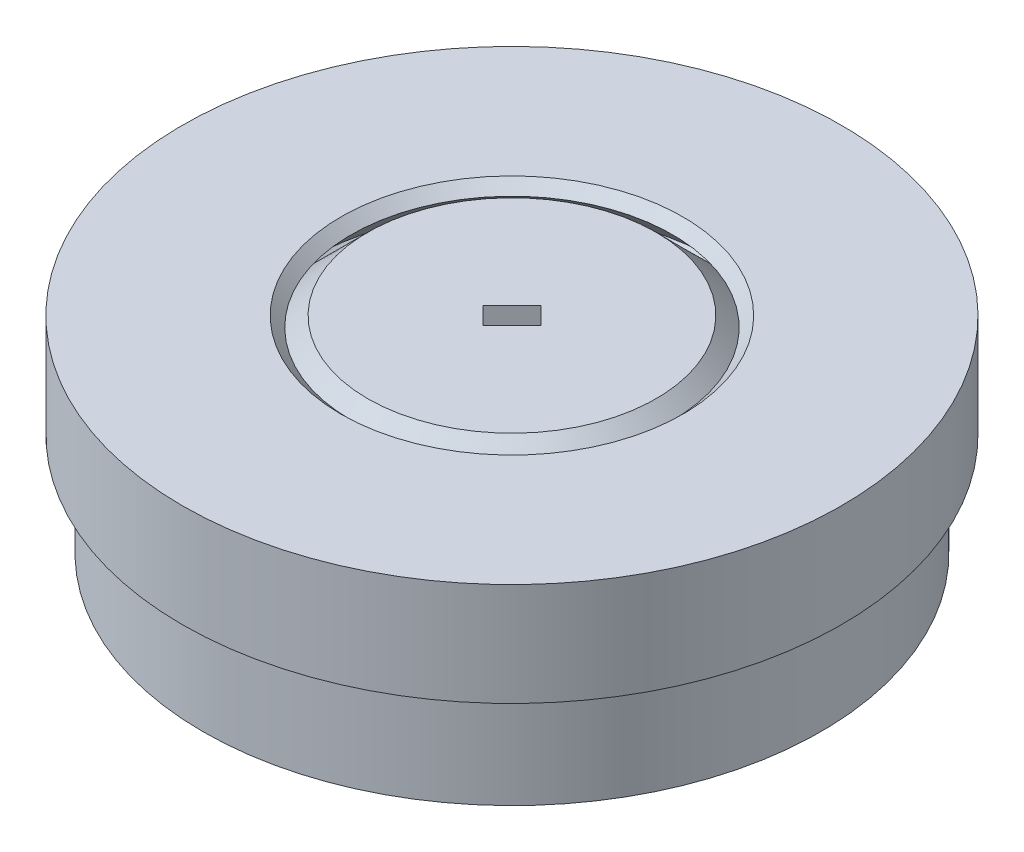
SolidWorks part; units mm, degrees
ref_plane "Front Plane" through (0, 0, 0) normal (0, 0, 1) x (1, 0, 0)
ref_plane "Top Plane" through (0, 0, 0) normal (0, 1, 0) x (1, 0, 0)
ref_plane "Right Plane" through (0, 0, 0) normal (1, 0, 0) x (0, 0, -1)
sketch "Sketch3" plane through (0, 0, 0) normal (0, 1, 0) x (1, 0, 0)
  line L0 (0, 0) -> (0, 14) construction
  line L1 (0, 11) -> (0, 14)
  line L2 (6.4656, 8.8992) -> (8.229, 11.3262)
  line L3 (10.4616, 3.3992) -> (13.3148, 4.3262)
  line L4 (10.4616, -3.3992) -> (13.3148, -4.3262)
  line L5 (6.4656, -8.8992) -> (8.229, -11.3262)
  line L6 (0, -11) -> (0, -14)
  line L7 (-6.4656, -8.8992) -> (-8.229, -11.3262)
  line L8 (-10.4616, -3.3992) -> (-13.3148, -4.3262)
  line L9 (-10.4616, 3.3992) -> (-13.3148, 4.3262)
  line L10 (-6.4656, 8.8992) -> (-8.229, 11.3262)
  line L12 (2, 2) -> (-2, 2)
  line L13 (2, 2) -> (2, -2)
  line L14 (2, -2) -> (-2, -2)
  line L15 (-2, 2) -> (-2, -2)
  line L16 (0, -2) -> (0, 2) construction
  line L17 (2, 0) -> (-2, 0) construction
  circle A0 centre (0, 0) radius 15
  circle A1 centre (0, 0) radius 14 construction
  spline S0 degree 4 poles (-0.6778, 10.6763) (-0.6286, 10.7014) (-0.5336, 10.7495) (-0.4182, 10.8106) (-0.084, 10.9641) (0.0577, 11.0264) (0.4379, 11.1818) (0.6637, 11.2619) (0.971, 11.3685) (1.234, 11.4472) (1.5272, 11.5305) (1.8056, 11.5989) (2.0959, 11.6642) (2.3817, 11.7192) (2.6725, 11.7684) (2.9623, 11.8092) (3.2542, 11.8431) (3.5945, 11.8737) (4.009, 11.8986) (4.4979, 11.9088) (4.9859, 11.897) (5.4262, 11.8684) (5.7898, 11.8338) (6.0839, 11.7981) (6.4416, 11.7478) (6.8131, 11.6815) (7.1561, 11.6125) (7.5364, 11.5205) (7.7792, 11.459) (8.1801, 11.3427) (8.3369, 11.2932) (8.7269, 11.165) (8.8594, 11.1137) (8.9726, 11.0725) (9.0307, 11.0511) knots 0 0 0 0 0 0.018755 0.037509 0.074516 0.103872 0.133229 0.162585 0.191942 0.221299 0.250655 0.280012 0.309368 0.338725 0.368082 0.397438 0.426795 0.456151 0.504872 0.563586 0.622299 0.651656 0.681012 0.710369 0.739725 0.798439 0.827795 0.857152 0.886508 0.915865 0.957933 0.978966 1 1 1 1 1 construction
  spline S1 degree 4 poles (0, 11) (0.0566, 11.0246) (0.1702, 11.0724) (0.4379, 11.1818) (0.6637, 11.2619) (0.971, 11.3685) (1.234, 11.4472) (1.5272, 11.5305) (1.8056, 11.5989) (2.0959, 11.6642) (2.3817, 11.7192) (2.6725, 11.7684) (2.9623, 11.8092) (3.2542, 11.8431) (3.5945, 11.8737) (4.009, 11.8986) (4.4979, 11.9088) (4.9859, 11.897) (5.4262, 11.8684) (5.7898, 11.8338) (6.0839, 11.7981) (6.4416, 11.7478) (6.8131, 11.6815) (7.1561, 11.6125) (7.5364, 11.5205) (7.7792, 11.459) (8.0505, 11.3803) (8.17, 11.3445) (8.229, 11.3262) knots 0.074516 0.074516 0.074516 0.074516 0.074516 0.103872 0.133229 0.162585 0.191942 0.221299 0.250655 0.280012 0.309368 0.338725 0.368082 0.397438 0.426795 0.456151 0.504872 0.563586 0.622299 0.651656 0.681012 0.710369 0.739725 0.798439 0.827795 0.857152 0.886508 0.915865 0.915865 0.915865 0.915865 0.915865
  spline S2 degree 4 poles (5.727, 9.0357) (5.7816, 9.0271) (5.8867, 9.0101) (6.016, 8.9918) (6.3766, 8.9195) (6.5279, 8.8866) (6.9268, 8.7889) (7.1565, 8.7209) (7.4678, 8.6266) (7.7268, 8.5357) (8.013, 8.4307) (8.2785, 8.3224) (8.5517, 8.2045) (8.8152, 8.0811) (9.0794, 7.95) (9.3378, 7.8126) (9.5939, 7.6685) (9.8872, 7.4932) (10.2371, 7.2697) (10.6387, 6.9906) (11.0265, 6.6943) (11.3659, 6.4123) (11.6398, 6.1706) (11.8567, 5.9689) (12.1165, 5.7179) (12.3781, 5.4459) (12.6151, 5.1885) (12.8687, 4.8905) (13.029, 4.698) (13.2848, 4.3683) (13.3827, 4.236) (13.6228, 3.9031) (13.6999, 3.7838) (13.7672, 3.6839) (13.8017, 3.6324) knots 0 0 0 0 0 0.018755 0.037509 0.074516 0.103872 0.133229 0.162585 0.191942 0.221299 0.250655 0.280012 0.309368 0.338725 0.368082 0.397438 0.426795 0.456151 0.504872 0.563586 0.622299 0.651656 0.681012 0.710369 0.739725 0.798439 0.827795 0.857152 0.886508 0.915865 0.957933 0.978966 1 1 1 1 1 construction
  spline S3 degree 4 poles (6.4656, 8.8992) (6.5259, 8.8858) (6.6459, 8.8577) (6.9268, 8.7889) (7.1565, 8.7209) (7.4678, 8.6266) (7.7268, 8.5357) (8.013, 8.4307) (8.2785, 8.3224) (8.5517, 8.2045) (8.8152, 8.0811) (9.0794, 7.95) (9.3378, 7.8126) (9.5939, 7.6685) (9.8872, 7.4932) (10.2371, 7.2697) (10.6387, 6.9906) (11.0265, 6.6943) (11.3659, 6.4123) (11.6398, 6.1706) (11.8567, 5.9689) (12.1165, 5.7179) (12.3781, 5.4459) (12.6151, 5.1885) (12.8687, 4.8905) (13.029, 4.698) (13.2021, 4.4749) (13.2778, 4.3756) (13.3148, 4.3262) knots 0.074516 0.074516 0.074516 0.074516 0.074516 0.103872 0.133229 0.162585 0.191942 0.221299 0.250655 0.280012 0.309368 0.338725 0.368082 0.397438 0.426795 0.456151 0.504872 0.563586 0.622299 0.651656 0.681012 0.710369 0.739725 0.798439 0.827795 0.857152 0.886508 0.915865 0.915865 0.915865 0.915865 0.915865
  spline S4 degree 4 poles (9.9443, 3.9438) (9.9834, 3.9047) (10.0585, 3.8292) (10.1522, 3.7384) (10.4015, 3.468) (10.5046, 3.3524) (10.7698, 3.0389) (10.9158, 2.8489) (11.1122, 2.5895) (11.2683, 2.3638) (11.4381, 2.1106) (11.5892, 1.867) (11.7409, 1.6111) (11.8816, 1.3563) (12.0183, 1.095) (12.1466, 0.8319) (12.2691, 0.5648) (12.4033, 0.2506) (12.5551, -0.1359) (12.7158, -0.5977) (12.8555, -1.0654) (12.9643, -1.493) (13.0438, -1.8496) (13.1007, -2.1403) (13.1634, -2.496) (13.2151, -2.8698) (13.2555, -3.2174) (13.2855, -3.6076) (13.3021, -3.8575) (13.3153, -4.2746) (13.3167, -4.4391) (13.3153, -4.8496) (13.3075, -4.9915) (13.3032, -5.1118) (13.3009, -5.1737) knots 0 0 0 0 0 0.018755 0.037509 0.074516 0.103872 0.133229 0.162585 0.191942 0.221299 0.250655 0.280012 0.309368 0.338725 0.368082 0.397438 0.426795 0.456151 0.504872 0.563586 0.622299 0.651656 0.681012 0.710369 0.739725 0.798439 0.827795 0.857152 0.886508 0.915865 0.957933 0.978966 1 1 1 1 1 construction
  spline S5 degree 4 poles (10.4616, 3.3992) (10.5025, 3.3529) (10.583, 3.2597) (10.7698, 3.0389) (10.9158, 2.8489) (11.1122, 2.5895) (11.2683, 2.3638) (11.4381, 2.1106) (11.5892, 1.867) (11.7409, 1.6111) (11.8816, 1.3563) (12.0183, 1.095) (12.1466, 0.8319) (12.2691, 0.5648) (12.4033, 0.2506) (12.5551, -0.1359) (12.7158, -0.5977) (12.8555, -1.0654) (12.9643, -1.493) (13.0438, -1.8496) (13.1007, -2.1403) (13.1634, -2.496) (13.2151, -2.8698) (13.2555, -3.2174) (13.2855, -3.6076) (13.3021, -3.8575) (13.311, -4.1398) (13.3139, -4.2645) (13.3148, -4.3262) knots 0.074516 0.074516 0.074516 0.074516 0.074516 0.103872 0.133229 0.162585 0.191942 0.221299 0.250655 0.280012 0.309368 0.338725 0.368082 0.397438 0.426795 0.456151 0.504872 0.563586 0.622299 0.651656 0.681012 0.710369 0.739725 0.798439 0.827795 0.857152 0.886508 0.915865 0.915865 0.915865 0.915865 0.915865
  spline S6 degree 4 poles (10.3632, -2.6545) (10.3719, -2.7091) (10.3882, -2.8143) (10.4107, -2.9429) (10.4535, -3.3082) (10.4689, -3.4622) (10.4992, -3.8718) (10.5056, -4.1113) (10.512, -4.4366) (10.5056, -4.711) (10.4942, -5.0156) (10.4732, -5.3015) (10.4456, -5.5978) (10.4097, -5.8866) (10.3666, -6.1783) (10.3158, -6.4665) (10.2579, -6.7546) (10.1818, -7.0878) (10.0774, -7.4896) (9.936, -7.9578) (9.774, -8.4182) (9.6108, -8.8281) (9.4655, -9.1633) (9.3407, -9.4319) (9.1823, -9.7566) (9.0044, -10.0894) (8.8328, -10.3943) (8.6277, -10.7276) (8.4943, -10.9395) (8.2597, -11.2848) (8.1642, -11.4187) (7.9218, -11.7499) (7.8321, -11.8601) (7.7579, -11.955) (7.7196, -12.0037) knots 0 0 0 0 0 0.018755 0.037509 0.074516 0.103872 0.133229 0.162585 0.191942 0.221299 0.250655 0.280012 0.309368 0.338725 0.368082 0.397438 0.426795 0.456151 0.504872 0.563586 0.622299 0.651656 0.681012 0.710369 0.739725 0.798439 0.827795 0.857152 0.886508 0.915865 0.957933 0.978966 1 1 1 1 1 construction
  spline S7 degree 4 poles (10.4616, -3.3992) (10.4675, -3.4606) (10.4779, -3.5834) (10.4992, -3.8718) (10.5056, -4.1113) (10.512, -4.4366) (10.5056, -4.711) (10.4942, -5.0156) (10.4732, -5.3015) (10.4456, -5.5978) (10.4097, -5.8866) (10.3666, -6.1783) (10.3158, -6.4665) (10.2579, -6.7546) (10.1818, -7.0878) (10.0774, -7.4896) (9.936, -7.9578) (9.774, -8.4182) (9.6108, -8.8281) (9.4655, -9.1633) (9.3407, -9.4319) (9.1823, -9.7566) (9.0044, -10.0894) (8.8328, -10.3943) (8.6277, -10.7276) (8.4943, -10.9395) (8.3355, -11.1732) (8.2645, -11.2758) (8.229, -11.3262) knots 0.074516 0.074516 0.074516 0.074516 0.074516 0.103872 0.133229 0.162585 0.191942 0.221299 0.250655 0.280012 0.309368 0.338725 0.368082 0.397438 0.426795 0.456151 0.504872 0.563586 0.622299 0.651656 0.681012 0.710369 0.739725 0.798439 0.827795 0.857152 0.886508 0.915865 0.915865 0.915865 0.915865 0.915865
  spline S8 degree 4 poles (6.8238, -8.2389) (6.7987, -8.2881) (6.75, -8.3829) (6.6926, -8.5001) (6.5125, -8.8208) (6.4344, -8.9545) (6.2182, -9.3037) (6.0826, -9.5012) (5.8967, -9.7681) (5.7302, -9.9863) (5.5419, -10.2261) (5.3569, -10.445) (5.1604, -10.6685) (4.9615, -10.881) (4.7552, -11.0917) (4.5447, -11.295) (4.3285, -11.4941) (4.0712, -11.7188) (3.7505, -11.9826) (3.3609, -12.2782) (2.9593, -12.5555) (2.5862, -12.7912) (2.2717, -12.9769) (2.0128, -13.1209) (1.6938, -13.2904) (1.3544, -13.4552) (1.0362, -13.601) (0.6745, -13.7501) (0.4419, -13.8431) (0.0492, -13.9845) (-0.1068, -14.0367) (-0.4976, -14.1622) (-0.6349, -14.1986) (-0.7507, -14.2318) (-0.8103, -14.2487) knots 0 0 0 0 0 0.018755 0.037509 0.074516 0.103872 0.133229 0.162585 0.191942 0.221299 0.250655 0.280012 0.309368 0.338725 0.368082 0.397438 0.426795 0.456151 0.504872 0.563586 0.622299 0.651656 0.681012 0.710369 0.739725 0.798439 0.827795 0.857152 0.886508 0.915865 0.957933 0.978966 1 1 1 1 1 construction
  spline S9 degree 4 poles (6.4656, -8.8992) (6.4343, -8.9523) (6.3705, -9.0578) (6.2182, -9.3037) (6.0826, -9.5012) (5.8967, -9.7681) (5.7302, -9.9863) (5.5419, -10.2261) (5.3569, -10.445) (5.1604, -10.6685) (4.9615, -10.881) (4.7552, -11.0917) (4.5447, -11.295) (4.3285, -11.4941) (4.0712, -11.7188) (3.7505, -11.9826) (3.3609, -12.2782) (2.9593, -12.5555) (2.5862, -12.7912) (2.2717, -12.9769) (2.0128, -13.1209) (1.6938, -13.2904) (1.3544, -13.4552) (1.0362, -13.601) (0.6745, -13.7501) (0.4419, -13.8431) (0.1762, -13.9388) (0.0584, -13.9801) (0, -14) knots 0.074516 0.074516 0.074516 0.074516 0.074516 0.103872 0.133229 0.162585 0.191942 0.221299 0.250655 0.280012 0.309368 0.338725 0.368082 0.397438 0.426795 0.456151 0.504872 0.563586 0.622299 0.651656 0.681012 0.710369 0.739725 0.798439 0.827795 0.857152 0.886508 0.915865 0.915865 0.915865 0.915865 0.915865
  spline S10 degree 4 poles (0.6778, -10.6763) (0.6286, -10.7014) (0.5336, -10.7495) (0.4182, -10.8106) (0.084, -10.9641) (-0.0577, -11.0264) (-0.4379, -11.1818) (-0.6637, -11.2619) (-0.971, -11.3685) (-1.234, -11.4472) (-1.5272, -11.5305) (-1.8056, -11.5989) (-2.0959, -11.6642) (-2.3817, -11.7192) (-2.6725, -11.7684) (-2.9623, -11.8092) (-3.2542, -11.8431) (-3.5945, -11.8737) (-4.009, -11.8986) (-4.4979, -11.9088) (-4.9859, -11.897) (-5.4262, -11.8684) (-5.7898, -11.8338) (-6.0839, -11.7981) (-6.4416, -11.7478) (-6.8131, -11.6815) (-7.1561, -11.6125) (-7.5364, -11.5205) (-7.7792, -11.459) (-8.1801, -11.3427) (-8.3369, -11.2932) (-8.7269, -11.165) (-8.8594, -11.1137) (-8.9726, -11.0725) (-9.0307, -11.0511) knots 0 0 0 0 0 0.018755 0.037509 0.074516 0.103872 0.133229 0.162585 0.191942 0.221299 0.250655 0.280012 0.309368 0.338725 0.368082 0.397438 0.426795 0.456151 0.504872 0.563586 0.622299 0.651656 0.681012 0.710369 0.739725 0.798439 0.827795 0.857152 0.886508 0.915865 0.957933 0.978966 1 1 1 1 1 construction
  spline S11 degree 4 poles (0, -11) (-0.0566, -11.0246) (-0.1702, -11.0724) (-0.4379, -11.1818) (-0.6637, -11.2619) (-0.971, -11.3685) (-1.234, -11.4472) (-1.5272, -11.5305) (-1.8056, -11.5989) (-2.0959, -11.6642) (-2.3817, -11.7192) (-2.6725, -11.7684) (-2.9623, -11.8092) (-3.2542, -11.8431) (-3.5945, -11.8737) (-4.009, -11.8986) (-4.4979, -11.9088) (-4.9859, -11.897) (-5.4262, -11.8684) (-5.7898, -11.8338) (-6.0839, -11.7981) (-6.4416, -11.7478) (-6.8131, -11.6815) (-7.1561, -11.6125) (-7.5364, -11.5205) (-7.7792, -11.459) (-8.0505, -11.3803) (-8.17, -11.3445) (-8.229, -11.3262) knots 0.074516 0.074516 0.074516 0.074516 0.074516 0.103872 0.133229 0.162585 0.191942 0.221299 0.250655 0.280012 0.309368 0.338725 0.368082 0.397438 0.426795 0.456151 0.504872 0.563586 0.622299 0.651656 0.681012 0.710369 0.739725 0.798439 0.827795 0.857152 0.886508 0.915865 0.915865 0.915865 0.915865 0.915865
  spline S12 degree 4 poles (-5.727, -9.0357) (-5.7816, -9.0271) (-5.8867, -9.0101) (-6.016, -8.9918) (-6.3766, -8.9195) (-6.5279, -8.8866) (-6.9268, -8.7889) (-7.1565, -8.7209) (-7.4678, -8.6266) (-7.7268, -8.5357) (-8.013, -8.4307) (-8.2785, -8.3224) (-8.5517, -8.2045) (-8.8152, -8.0811) (-9.0794, -7.95) (-9.3378, -7.8126) (-9.5939, -7.6685) (-9.8872, -7.4932) (-10.2371, -7.2697) (-10.6387, -6.9906) (-11.0265, -6.6943) (-11.3659, -6.4123) (-11.6398, -6.1706) (-11.8567, -5.9689) (-12.1165, -5.7179) (-12.3781, -5.4459) (-12.6151, -5.1885) (-12.8687, -4.8905) (-13.029, -4.698) (-13.2848, -4.3683) (-13.3827, -4.236) (-13.6228, -3.9031) (-13.6999, -3.7838) (-13.7672, -3.6839) (-13.8017, -3.6324) knots 0 0 0 0 0 0.018755 0.037509 0.074516 0.103872 0.133229 0.162585 0.191942 0.221299 0.250655 0.280012 0.309368 0.338725 0.368082 0.397438 0.426795 0.456151 0.504872 0.563586 0.622299 0.651656 0.681012 0.710369 0.739725 0.798439 0.827795 0.857152 0.886508 0.915865 0.957933 0.978966 1 1 1 1 1 construction
  spline S13 degree 4 poles (-6.4656, -8.8992) (-6.5259, -8.8858) (-6.6459, -8.8577) (-6.9268, -8.7889) (-7.1565, -8.7209) (-7.4678, -8.6266) (-7.7268, -8.5357) (-8.013, -8.4307) (-8.2785, -8.3224) (-8.5517, -8.2045) (-8.8152, -8.0811) (-9.0794, -7.95) (-9.3378, -7.8126) (-9.5939, -7.6685) (-9.8872, -7.4932) (-10.2371, -7.2697) (-10.6387, -6.9906) (-11.0265, -6.6943) (-11.3659, -6.4123) (-11.6398, -6.1706) (-11.8567, -5.9689) (-12.1165, -5.7179) (-12.3781, -5.4459) (-12.6151, -5.1885) (-12.8687, -4.8905) (-13.029, -4.698) (-13.2021, -4.4749) (-13.2778, -4.3756) (-13.3148, -4.3262) knots 0.074516 0.074516 0.074516 0.074516 0.074516 0.103872 0.133229 0.162585 0.191942 0.221299 0.250655 0.280012 0.309368 0.338725 0.368082 0.397438 0.426795 0.456151 0.504872 0.563586 0.622299 0.651656 0.681012 0.710369 0.739725 0.798439 0.827795 0.857152 0.886508 0.915865 0.915865 0.915865 0.915865 0.915865
  spline S14 degree 4 poles (-9.9443, -3.9438) (-9.9834, -3.9047) (-10.0585, -3.8292) (-10.1522, -3.7384) (-10.4015, -3.468) (-10.5046, -3.3524) (-10.7698, -3.0389) (-10.9158, -2.8489) (-11.1122, -2.5895) (-11.2683, -2.3638) (-11.4381, -2.1106) (-11.5892, -1.867) (-11.7409, -1.6111) (-11.8816, -1.3563) (-12.0183, -1.095) (-12.1466, -0.8319) (-12.2691, -0.5648) (-12.4033, -0.2506) (-12.5551, 0.1359) (-12.7158, 0.5977) (-12.8555, 1.0654) (-12.9643, 1.493) (-13.0438, 1.8496) (-13.1007, 2.1403) (-13.1634, 2.496) (-13.2151, 2.8698) (-13.2555, 3.2174) (-13.2855, 3.6076) (-13.3021, 3.8575) (-13.3153, 4.2746) (-13.3167, 4.4391) (-13.3153, 4.8496) (-13.3075, 4.9915) (-13.3032, 5.1118) (-13.3009, 5.1737) knots 0 0 0 0 0 0.018755 0.037509 0.074516 0.103872 0.133229 0.162585 0.191942 0.221299 0.250655 0.280012 0.309368 0.338725 0.368082 0.397438 0.426795 0.456151 0.504872 0.563586 0.622299 0.651656 0.681012 0.710369 0.739725 0.798439 0.827795 0.857152 0.886508 0.915865 0.957933 0.978966 1 1 1 1 1 construction
  spline S15 degree 4 poles (-10.4616, -3.3992) (-10.5025, -3.3529) (-10.583, -3.2597) (-10.7698, -3.0389) (-10.9158, -2.8489) (-11.1122, -2.5895) (-11.2683, -2.3638) (-11.4381, -2.1106) (-11.5892, -1.867) (-11.7409, -1.6111) (-11.8816, -1.3563) (-12.0183, -1.095) (-12.1466, -0.8319) (-12.2691, -0.5648) (-12.4033, -0.2506) (-12.5551, 0.1359) (-12.7158, 0.5977) (-12.8555, 1.0654) (-12.9643, 1.493) (-13.0438, 1.8496) (-13.1007, 2.1403) (-13.1634, 2.496) (-13.2151, 2.8698) (-13.2555, 3.2174) (-13.2855, 3.6076) (-13.3021, 3.8575) (-13.311, 4.1398) (-13.3139, 4.2645) (-13.3148, 4.3262) knots 0.074516 0.074516 0.074516 0.074516 0.074516 0.103872 0.133229 0.162585 0.191942 0.221299 0.250655 0.280012 0.309368 0.338725 0.368082 0.397438 0.426795 0.456151 0.504872 0.563586 0.622299 0.651656 0.681012 0.710369 0.739725 0.798439 0.827795 0.857152 0.886508 0.915865 0.915865 0.915865 0.915865 0.915865
  spline S16 degree 4 poles (-10.3632, 2.6545) (-10.3719, 2.7091) (-10.3882, 2.8143) (-10.4107, 2.9429) (-10.4535, 3.3082) (-10.4689, 3.4622) (-10.4992, 3.8718) (-10.5056, 4.1113) (-10.512, 4.4366) (-10.5056, 4.711) (-10.4942, 5.0156) (-10.4732, 5.3015) (-10.4456, 5.5978) (-10.4097, 5.8866) (-10.3666, 6.1783) (-10.3158, 6.4665) (-10.2579, 6.7546) (-10.1818, 7.0878) (-10.0774, 7.4896) (-9.936, 7.9578) (-9.774, 8.4182) (-9.6108, 8.8281) (-9.4655, 9.1633) (-9.3407, 9.4319) (-9.1823, 9.7566) (-9.0044, 10.0894) (-8.8328, 10.3943) (-8.6277, 10.7276) (-8.4943, 10.9395) (-8.2597, 11.2848) (-8.1642, 11.4187) (-7.9218, 11.7499) (-7.8321, 11.8601) (-7.7579, 11.955) (-7.7196, 12.0037) knots 0 0 0 0 0 0.018755 0.037509 0.074516 0.103872 0.133229 0.162585 0.191942 0.221299 0.250655 0.280012 0.309368 0.338725 0.368082 0.397438 0.426795 0.456151 0.504872 0.563586 0.622299 0.651656 0.681012 0.710369 0.739725 0.798439 0.827795 0.857152 0.886508 0.915865 0.957933 0.978966 1 1 1 1 1 construction
  spline S17 degree 4 poles (-10.4616, 3.3992) (-10.4675, 3.4606) (-10.4779, 3.5834) (-10.4992, 3.8718) (-10.5056, 4.1113) (-10.512, 4.4366) (-10.5056, 4.711) (-10.4942, 5.0156) (-10.4732, 5.3015) (-10.4456, 5.5978) (-10.4097, 5.8866) (-10.3666, 6.1783) (-10.3158, 6.4665) (-10.2579, 6.7546) (-10.1818, 7.0878) (-10.0774, 7.4896) (-9.936, 7.9578) (-9.774, 8.4182) (-9.6108, 8.8281) (-9.4655, 9.1633) (-9.3407, 9.4319) (-9.1823, 9.7566) (-9.0044, 10.0894) (-8.8328, 10.3943) (-8.6277, 10.7276) (-8.4943, 10.9395) (-8.3355, 11.1732) (-8.2645, 11.2758) (-8.229, 11.3262) knots 0.074516 0.074516 0.074516 0.074516 0.074516 0.103872 0.133229 0.162585 0.191942 0.221299 0.250655 0.280012 0.309368 0.338725 0.368082 0.397438 0.426795 0.456151 0.504872 0.563586 0.622299 0.651656 0.681012 0.710369 0.739725 0.798439 0.827795 0.857152 0.886508 0.915865 0.915865 0.915865 0.915865 0.915865
  spline S18 degree 4 poles (-6.8238, 8.2389) (-6.7987, 8.2881) (-6.75, 8.3829) (-6.6926, 8.5001) (-6.5125, 8.8208) (-6.4344, 8.9545) (-6.2182, 9.3037) (-6.0826, 9.5012) (-5.8967, 9.7681) (-5.7302, 9.9863) (-5.5419, 10.2261) (-5.3569, 10.445) (-5.1604, 10.6685) (-4.9615, 10.881) (-4.7552, 11.0917) (-4.5447, 11.295) (-4.3285, 11.4941) (-4.0712, 11.7188) (-3.7505, 11.9826) (-3.3609, 12.2782) (-2.9593, 12.5555) (-2.5862, 12.7912) (-2.2717, 12.9769) (-2.0128, 13.1209) (-1.6938, 13.2904) (-1.3544, 13.4552) (-1.0362, 13.601) (-0.6745, 13.7501) (-0.4419, 13.8431) (-0.0492, 13.9845) (0.1068, 14.0367) (0.4976, 14.1622) (0.6349, 14.1986) (0.7507, 14.2318) (0.8103, 14.2487) knots 0 0 0 0 0 0.018755 0.037509 0.074516 0.103872 0.133229 0.162585 0.191942 0.221299 0.250655 0.280012 0.309368 0.338725 0.368082 0.397438 0.426795 0.456151 0.504872 0.563586 0.622299 0.651656 0.681012 0.710369 0.739725 0.798439 0.827795 0.857152 0.886508 0.915865 0.957933 0.978966 1 1 1 1 1 construction
  spline S19 degree 4 poles (-6.4656, 8.8992) (-6.4343, 8.9523) (-6.3705, 9.0578) (-6.2182, 9.3037) (-6.0826, 9.5012) (-5.8967, 9.7681) (-5.7302, 9.9863) (-5.5419, 10.2261) (-5.3569, 10.445) (-5.1604, 10.6685) (-4.9615, 10.881) (-4.7552, 11.0917) (-4.5447, 11.295) (-4.3285, 11.4941) (-4.0712, 11.7188) (-3.7505, 11.9826) (-3.3609, 12.2782) (-2.9593, 12.5555) (-2.5862, 12.7912) (-2.2717, 12.9769) (-2.0128, 13.1209) (-1.6938, 13.2904) (-1.3544, 13.4552) (-1.0362, 13.601) (-0.6745, 13.7501) (-0.4419, 13.8431) (-0.1762, 13.9388) (-0.0584, 13.9801) (0, 14) knots 0.074516 0.074516 0.074516 0.074516 0.074516 0.103872 0.133229 0.162585 0.191942 0.221299 0.250655 0.280012 0.309368 0.338725 0.368082 0.397438 0.426795 0.456151 0.504872 0.563586 0.622299 0.651656 0.681012 0.710369 0.739725 0.798439 0.827795 0.857152 0.886508 0.915865 0.915865 0.915865 0.915865 0.915865
  point P57 (0, 0)
  dimension "D1" = 30
  dimension "D2" = 28
  dimension "D3" = 10
  dimension "D4" = 4
  dimension "D5" = 4
extrude "Boss-Extrude1" add sketch "Sketch3" along normal blind 3 contours A0 L10 S19 L1 S1 L2 S3 L3 S5 L4 S7 L5 S9 L6 S11 L7 S13 L8 S15 L9 S17 | L13 L12 L15 L14 region at (-14.5757, 0, 0)
sketch "Sketch5" plane through (0, 0, 0) normal (1, 0, 0) x (0, 0, -1)
  line L0 (-2, 0) -> (-2, 3) construction
  line L1 (-2, 3) -> (2, 3) construction
  line L2 (2, 3) -> (2, 0) construction
  line L3 (2, 0) -> (-2, 0) construction
  line L4 (-2, 3) -> (2, 0) construction
  line L5 (-2, 0) -> (2, 3) construction
  line L6 (15, 0) -> (15, 3) construction
  line L7 (-15, 3) -> (15, 3) construction
  line L8 (-15, 3) -> (-15, 10) construction
  line L9 (-15, 10) -> (15, 10) construction
  line L10 (15, 3) -> (15, 10) construction
  line L11 (0, 10) -> (0, 3) construction
  line L12 (-15, 6.5) -> (15, 6.5) construction
  line L13 (15, 5) -> (16, 5) construction
  line L14 (-15, 10) -> (-16, 10) construction
  line L15 (-15, 10) -> (-15, 5) construction
  line L16 (-15, 5) -> (-16, 5) construction
  line L17 (-16, 10) -> (-16, 5) construction
  line L18 (-15.5, 5) -> (-15.5, 10) construction
  line L19 (-15, 7.5) -> (-16, 7.5) construction
  line L20 (15, 10) -> (16, 10) construction
  line L21 (16, 10) -> (16, 5) construction
  line L22 (-7, 10) -> (-9.5, 7.5)
  line L23 (7, 3) -> (-7, 3) construction
  line L24 (7, 3) -> (7, 10) construction
  line L25 (7, 10) -> (-7, 10) construction
  line L26 (-7, 3) -> (-7, 10) construction
  line L27 (0, 10) -> (0, 3) construction
  line L28 (7, 6.5) -> (-7, 6.5) construction
  line L29 (-7, 10) -> (7, 10) construction
  line L30 (-7, 10) -> (-7, 5) construction
  line L31 (-7, 5) -> (7, 5) construction
  line L32 (7, 10) -> (7, 5) construction
  line L33 (0, 5) -> (0, 10) construction
  line L34 (-7, 7.5) -> (7, 7.5) construction
  line L35 (7.3, 5) -> (-7.3, 5) construction
  line L36 (7.3, 5) -> (7.3, 10) construction
  line L37 (7.3, 10) -> (-7.3, 10) construction
  line L38 (-7.3, 5) -> (-7.3, 10) construction
  line L39 (0, 10) -> (0, 5) construction
  line L40 (7.3, 7.5) -> (-7.3, 7.5) construction
  line L41 (-9.5, 7.5) -> (-7, 5)
  line L42 (-7.3, 10) -> (-9.8, 7.5)
  line L43 (-9.8, 7.5) -> (-7.3, 5)
  line L44 (-7, 10) -> (0, 10)
  line L45 (0, 10) -> (0, 3)
  line L48 (-7, 5) -> (-7, 3)
  line L52 (-7.3, 5) -> (-9.8, 5)
  line L53 (-9.8, 5) -> (-9.8, 3)
  line L54 (-9.8, 3) -> (-15, 3)
  line L55 (-15, 3) -> (-15, 5)
  line L56 (-15, 5) -> (-16, 5)
  line L57 (-16, 5) -> (-16, 10)
  line L58 (-16, 10) -> (-7.3, 10)
  line L59 (0, 3) -> (-7, 3)
  point P20 (0, 6.5)
  point P27 (0, 7.5)
  point P289 (-15.5, 7.5)
  point P440 (0, 6.5)
  point P493 (0, 7.5)
  dimension "D1" = 7
  dimension "D2" = 5
  dimension "D3" = 1
  dimension "D4" = 14
  dimension "D5" = 5
  dimension "D6" = 0.3
  dimension "D7" = 90
  dimension "D8" = 90
  dimension "D9" = 2.5
revolve "Revolve1" add sketch "Sketch5" angle 360 about L45
fillet "Fillet2" radius 0.5 1 edges at (0, 3, 9.8)
fillet "Fillet3" radius 0.5 1 edges at (0, 3, 7)
chamfer "Chamfer1" distance 0.5 angle 45 4 edges at (2, 0, 0) (0, 0, -2) (-2, 0, 0) (0, 0, 2)
chamfer "Chamfer2" distance 1 angle 45 1 edges at (0, 10, 7.3) first distance on face at (0, 10, 16)
sketch "Sketch6" plane through (0, 0, 0) normal (0, -1, 0) x (1, 0, 0)
  line L0 (1.5, -1.5) -> (-1.5, 1.5) construction
  line L1 (-0.2828, 1.1314) -> (1.1314, -0.2828)
  line L2 (-0.2828, 1.1314) -> (-1.1314, 0.2828)
  line L3 (1.1314, -0.2828) -> (0.2828, -1.1314)
  line L4 (-1.1314, 0.2828) -> (0.2828, -1.1314)
  line L5 (-0.2828, 1.1314) -> (0.2828, -1.1314) construction
  line L6 (1.1314, -0.2828) -> (-1.1314, 0.2828) construction
  point P5 (0, 0)
  dimension "D1" = 1.2
  dimension "D2" = 2
extrude "Cut-Extrude1" cut sketch "Sketch6" against normal through all
